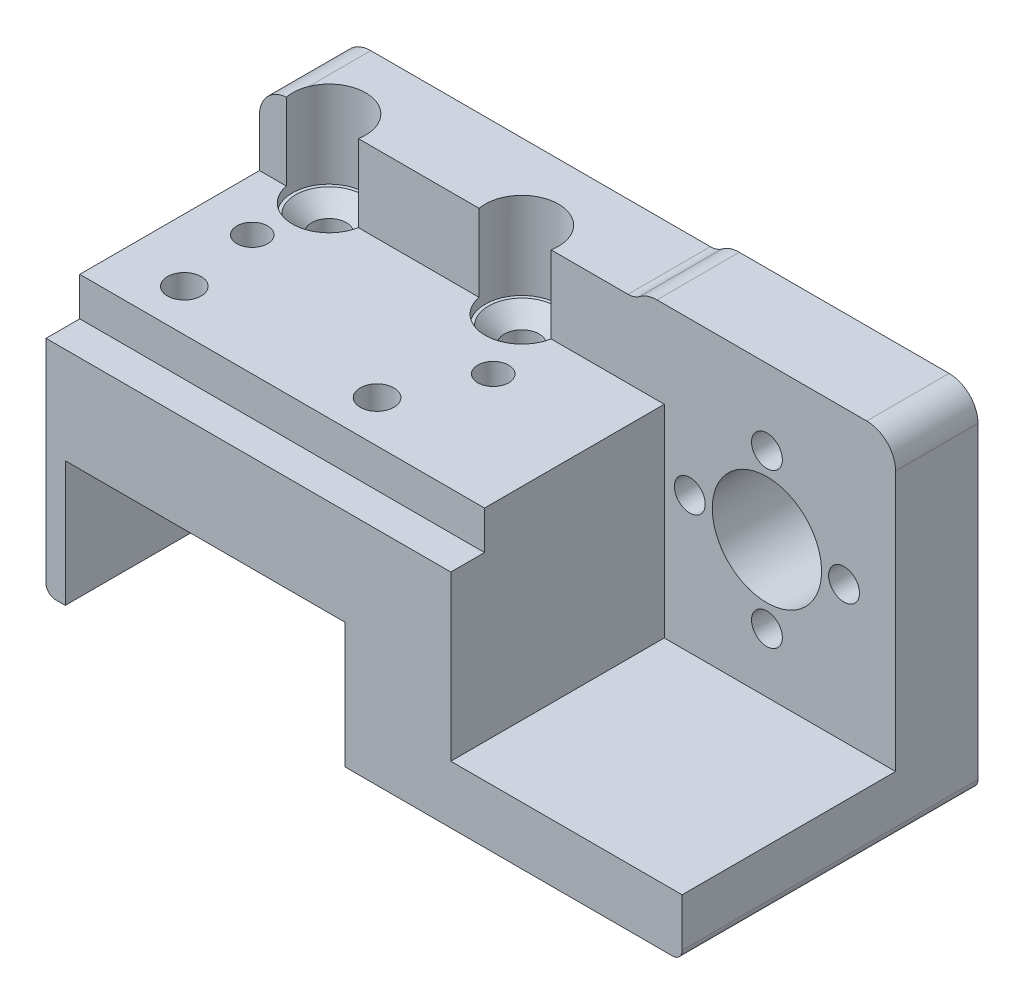
SolidWorks part; units mm, degrees
ref_plane "Front Plane" through (0, 0, 0) normal (0, 0, 1) x (1, 0, 0)
ref_plane "Top Plane" through (0, 0, 0) normal (0, 1, 0) x (1, 0, 0)
ref_plane "Right Plane" through (0, 0, 0) normal (1, 0, 0) x (0, 0, -1)
sketch "Croquis2" plane through (0, 0, 0) normal (0, 0, 1) x (1, 0, 0)
  line L0 (-42.15, -17.65) -> (-49.65, -17.65) construction
  line L1 (-42.15, -17.65) -> (-49.65, -17.65) construction
  line L2 (-49.65, -7.65) -> (-49.65, -17.65) construction
  line L3 (-49.65, -7.65) -> (-49.65, -17.65) construction
  line L5 (-52.65, -20.15) -> (13.35, -20.15)
  line L6 (-52.65, -20.15) -> (-52.65, 15.85)
  line L7 (-52.65, 15.85) -> (13.35, 15.85)
  line L8 (13.35, -20.15) -> (13.35, 15.85)
  line L9 (-50.65, -7.65) -> (-50.65, -7.15)
  line L10 (-21.65, -7.65) -> (-21.65, -17.65)
  line L11 (-21.65, -7.65) -> (-21.65, -20.15)
  line L13 (-50.65, -7.15) -> (-49.65, -7.15)
  line L14 (-21.65, -7.65) -> (-21.65, -7.15)
  line L15 (-21.65, -7.15) -> (-22.65, -7.15)
  line L16 (-50.65, -20.15) -> (-21.65, -20.15)
  line L17 (-30.45, -21.15) -> (-41.85, -21.15) construction
  line L18 (-49.65, -7.15) -> (-22.65, -7.15)
  line L19 (-49.65, -7.15) -> (-22.65, -7.15)
  line L28 (-50.65, -7.65) -> (-50.65, -17.65)
  line L29 (-50.65, -7.65) -> (-50.65, -20.15)
  circle A2 centre (0, 0) radius 5.67
  circle A3 centre (0, 0) radius 5.67
  circle A5 centre (0, 8) radius 1.3
  circle A6 centre (0, 8) radius 1.3
  circle A8 centre (8, 0) radius 1.3
  circle A9 centre (8, 0) radius 1.3
  circle A11 centre (0, -8) radius 1.3
  circle A12 centre (0, -8) radius 1.3
  circle A14 centre (-8, 0) radius 1.3
  circle A15 centre (-8, 0) radius 1.3
  circle M7 centre (0, 8) radius 1.6
  circle M8 centre (0, -8) radius 1.6
  circle M9 centre (8, 0) radius 1.6
  circle M10 centre (-8, 0) radius 1.6
  circle M12 centre (0, 0) radius 10.875
  dimension "D6" = 3
  dimension "D7" = 66
  dimension "D8" = 36
  dimension "D12" = 1
  dimension "D1" = 0.5
  dimension "D2" = 0.3
  dimension "D3" = 0.3
  dimension "D4" = 0.3
  dimension "D5" = 0.3
  dimension "D9" = 0.5
  dimension "D10" = 1
  dimension "D11" = 1
extrude "Saliente-Extruir1" add sketch "Croquis2" along normal offset from surface (30.7 mm away) 2 contours L29 L9 L13 L19 L15 L14 L11 L5 L8 L7 L6 M12 | A3 M12 M8 M10 M9 M7 region at (-20.3138, 0.0231, 0) region at (-10.5674, 0, 0)
sketch "Croquis4" plane through (0, 0, 30.7) normal (0, 0, 1) x (1, 0, 0)
  line L0 (-52.65, 15.85) -> (13.35, 15.85) construction
  line L1 (-10.65, 15.85) -> (13.35, 15.85)
  line L2 (-10.65, 15.85) -> (-10.65, -14.15)
  line L3 (-10.65, -14.15) -> (13.35, -14.15)
  line L4 (13.35, 15.85) -> (13.35, -14.15)
  line L5 (13.35, -20.15) -> (13.35, 15.85) construction
  line M9 (13.35, -20.15) -> (13.35, 15.85)
  line M10 (13.35, 15.85) -> (-52.65, 15.85)
  circle M13 centre (0, 0) radius 5.67
  circle M14 centre (0, -8) radius 1.6
  circle M15 centre (-8, 0) radius 1.6
  circle M16 centre (8, 0) radius 1.6
  circle M17 centre (0, 8) radius 1.6
  dimension "D1" = 24
  dimension "D2" = 30
extrude "Cortar-Extruir2" cut sketch "Croquis4" against normal offset from surface (22.7 mm away) 8 contours L2 L3 M9 M10 M13 M15 M17 M16 M14 region at (1.35, 15.4658, 30.7) up to face at (-27.9, -7.9, 0)
sketch "Croquis6" plane through (0, 0, 30.7) normal (0, 0, 1) x (1, 0, 0)
  line L0 (-30.15, -17.65) -> (-30.15, -13.15) construction
  line L1 (-21.65, -20.15) -> (-50.65, -20.15)
  line L2 (-21.65, -20.15) -> (-21.65, -7.15)
  line L3 (-21.65, -7.15) -> (-50.65, -7.15)
  line L4 (-50.65, -20.15) -> (-50.65, -7.15)
  line L5 (-30.15, -13.15) -> (-42.15, -13.15) construction
  line L6 (-42.15, -13.15) -> (-42.15, -17.65) construction
  line L7 (-29.65, -20.15) -> (-29.65, -12.65)
  line L8 (-29.65, -12.65) -> (-42.65, -12.65)
  line L9 (-42.65, -12.65) -> (-42.65, -20.15)
  line L10 (-29.65, -17.65) -> (-29.65, -12.65) construction
  line L11 (-42.65, -12.65) -> (-42.65, -17.65) construction
  dimension "D1" = 0.5
sketch "Croquis3" plane through (-52.65, 0, 0) normal (-1, 0, 0) x (0, 0, 1)
  line L0 (-2, -7.65) -> (32.7, -7.65) construction
  line L1 (20.85, 6.85) -> (8.55, 6.85)
  line L2 (20.85, 6.85) -> (20.85, 14.85)
  line L3 (20.85, 14.85) -> (8.55, 14.85)
  line L4 (8.55, 6.85) -> (8.55, 14.85)
  line L5 (0, -20.15) -> (0, 15.85) construction
  line L6 (30.7, 15.85) -> (30.7, -20.15) construction
  dimension "D1" = 8
  dimension "D2" = 12.3
  dimension "D3" = 14.5
  dimension "D4" = 9.85
  dimension "D5" = 8.55
extrude "Cortar-Extruir5" cut sketch "Croquis3" against normal blind 42
sketch "Croquis5" plane through (0, 15.85, 0) normal (0, 1, 0) x (1, 0, 0)
  line L2 (-52.65, -14.7) -> (-11.635, -14.7) construction
  line L3 (-10.65, -8.55) -> (-10.65, -20.85) construction
  line L4 (-52.65, -8.55) -> (-52.65, -20.85) construction
  line L5 (-52.65, -8.55) -> (-52.65, -20.85)
  circle A0 centre (-47.25, -14.7) radius 1.6
  circle A1 centre (-22.25, -14.7) radius 1.6
  point P10 (-52.65, -14.7)
  dimension "D3" = 3.2
  dimension "D1" = 11.6
  dimension "D2" = 25
extrude "Cortar-Extruir6" cut sketch "Croquis5" against normal through all contours L2 A0 | A0 L2 | A1 L2 | L2 A1 region at (-47.25, 15.85, 14.0209) region at (-22.25, 15.85, 14.0209) region at (-22.25, 15.85, 15.3791) region at (-47.25, 15.85, 15.3791)
sketch "Croquis7" plane through (0, 15.85, 0) normal (0, 1, 0) x (1, 0, 0)
  line L0 (-52.65, 0) -> (13.35, 0) construction
  line L1 (-52.65, -30.7) -> (-10.65, -30.7)
  line L2 (-52.65, -30.7) -> (-52.65, 0)
  line L3 (-52.65, 0) -> (-10.65, 0)
  line L4 (-10.65, -30.7) -> (-10.65, 0)
  line L5 (-52.65, -8.55) -> (-52.65, -20.85) construction
  line L6 (-52.65, -8.55) -> (-52.65, -20.85)
  line L8 (-52.65, -20.85) -> (-10.65, -20.85)
  line L9 (-52.65, -20.85) -> (-52.65, -30.7)
  line L10 (-52.65, -30.7) -> (-10.65, -30.7)
  line L11 (-10.65, -20.85) -> (-10.65, -30.7)
  line M3 (-10.65, -30.7) -> (-10.65, -8)
  line M6 (13.35, 0) -> (-52.65, 0)
  line M7 (-52.65, 0) -> (-52.65, -30.7)
  line M8 (-52.65, -30.7) -> (-10.65, -30.7)
  circle M15 centre (-47.25, -14.7) radius 1.6
  circle M16 centre (-22.25, -14.7) radius 1.6
extrude "Cortar-Extruir7" cut sketch "Croquis7" against normal up to surface (1 mm away) contours L2 L8 L4 M6 M7 M16 M15 region at (-31.592, 15.85, 10.345) up to face at (-47.25, 14.85, 16.3)
sketch "Croquis9" plane through (-10.65, 0, 0) normal (-1, 0, 0) x (0, 0, 1)
  line L4 (8, 14.85) -> (8, 15.85)
  line L5 (8, 15.85) -> (0, 15.85)
  line L6 (0, 15.85) -> (0, 14.85)
  line L7 (0, 14.85) -> (8, 14.85)
  line L8 (8, 14.85) -> (8, 15.85)
  line L9 (8, 15.85) -> (0, 15.85)
  line L10 (0, 15.85) -> (0, 14.85)
  line L11 (0, 14.85) -> (8, 14.85)
  dimension "D1" = 0
extrude "Saliente-Extruir4" add sketch "Croquis9" along normal blind 3
extrude "Cortar-Extruir8" cut sketch "Croquis7<3>" against normal up to surface (9 mm away) contours L8 M7 M8 M3 region at (-31.65, 15.85, 25.775) up to face at (-47.25, 6.85, 13.1)
sketch "Croquis7<3>" plane through (0, 15.85, 0) normal (0, 1, 0) x (1, 0, 0) same geometry as "Croquis7"
sketch "Croquis11" plane through (0, 6.85, 0) normal (0, 1, 0) x (1, 0, 0)
  line L1 (-47.25, -10.3121) -> (-51.05, -12.5061)
  line L2 (-51.05, -12.5061) -> (-51.05, -16.8939)
  line L3 (-51.05, -16.8939) -> (-47.25, -19.0879)
  line L4 (-47.25, -19.0879) -> (-43.45, -16.8939)
  line L5 (-43.45, -16.8939) -> (-43.45, -12.5061)
  line L6 (-43.45, -12.5061) -> (-47.25, -10.3121)
  line L7 (-22.25, -10.3121) -> (-26.05, -12.5061)
  line L8 (-26.05, -12.5061) -> (-26.05, -16.8939)
  line L9 (-26.05, -16.8939) -> (-22.25, -19.0879)
  line L10 (-22.25, -19.0879) -> (-18.45, -16.8939)
  line L11 (-18.45, -16.8939) -> (-18.45, -12.5061)
  line L12 (-18.45, -12.5061) -> (-22.25, -10.3121)
  circle A0 centre (-46.1299, -7.85) radius 1.5 construction
  circle A1 centre (-26.1299, -7.85) radius 1.5 construction
  circle A2 centre (-26.15, -22.85) radius 1.5 construction
  circle A3 centre (-46.15, -22.85) radius 1.5 construction
  circle A4 centre (-46.1299, -7.85) radius 1.5 construction
  circle A5 centre (-26.1299, -7.85) radius 1.5 construction
  circle A6 centre (-26.15, -22.85) radius 1.5 construction
  circle A7 centre (-46.15, -22.85) radius 1.5 construction
  circle A8 centre (-46.1299, -7.85) radius 3.8
  circle A9 centre (-26.1299, -7.85) radius 3.8
  circle A10 centre (-26.15, -22.85) radius 3.8
  circle A11 centre (-46.15, -22.85) radius 3.8
  circle A12 centre (-47.25, -14.7) radius 3.8 construction
  circle A13 centre (-22.25, -14.7) radius 3.8 construction
  circle A14 centre (-46.1299, -7.85) radius 1.75
  circle A15 centre (-26.1299, -7.85) radius 1.75
  circle A16 centre (-26.15, -22.85) radius 1.75
  circle A17 centre (-46.15, -22.85) radius 1.75
  circle M13 centre (-47.25, -14.7) radius 1.6
  circle M14 centre (-22.25, -14.7) radius 1.6
  line M18 (-10.65, -8.55) -> (-52.65, -8.55)
  dimension "D1" = 7.6
  dimension "D2" = 7.6
  dimension "D3" = 3.5
extrude "Cortar-Extruir9" cut sketch "Croquis11" against normal offset from surface (9 mm away) 1 from surface contours A14 A8 M18 | A14 A8 L1 L6 M18 | L1 A8 L6 | A14 M18 | A14 M18 | A15 A9 M18 | A15 M18 | A15 M18 | A15 A9 M18 region at (-46.8614, 6.85, 11.0938) region at (-46.0098, 6.85, 9.8058) region at (-26.4732, 6.85, 4.1542) region at (-26.1299, 6.85, 9.9873) region at (-46.4732, 6.85, 4.1542) region at (-46.1299, 6.85, 8.9831) region at (-46.1299, 6.85, 7.4676) region at (-26.1299, 6.85, 8.9831) region at (-26.1299, 6.85, 7.4676) up to face at (-47.25, 6.85, 13.1) offset beyond the face yes starting at face at (-25.65, 14.85, 5.5167)
extrude "Cortar-Extruir10" cut sketch "Croquis11<3>" against normal through all contours A14 M18 | A14 M18 | A15 M18 | A15 M18 | A16 | A17 region at (-46.1299, 6.85, 8.9831) region at (-46.1299, 6.85, 7.4676) region at (-26.1299, 6.85, 8.9831) region at (-26.1299, 6.85, 7.4676) region at (-26.15, 6.85, 22.85) region at (-46.15, 6.85, 22.85)
sketch "Croquis11<3>" plane through (0, 6.85, 0) normal (0, 1, 0) x (1, 0, 0) same geometry as "Croquis11"
extrude "Cortar-Extruir11" cut sketch "Croquis11<4>" along normal blind 4 and the other way through all from surface contours A8 L1 L2 L3 L4 L5 L6 M13 | L11 L12 L7 L8 L9 L10 M14 | L1 A8 L6 region at (-46.8614, 6.85, 11.0938) region at (-46.8317, 6.85, 11.6979) region at (-20.408, 6.85, 11.5096) starting at face at (-46.15, -7.15, 24.6)
sketch "Croquis11<4>" plane through (0, 6.85, 0) normal (0, 1, 0) x (1, 0, 0) same geometry as "Croquis11"
hole_wizard "Avellanado para tornillo con cabeza avellanada de clavija hexagonal de M31" positions "Croquis16" profile "Croquis17" countersink size "M3" standard "DIN" end condition through all
sketch "Croquis16" plane through (0, 5.85, 0) normal (0, 1, 0) x (1, 0, 0)
  point P0 (-46.1299, -7.85)
  point P3 (-26.1299, -7.85)
sketch "Croquis17" plane through (-46.1299, 5.85, 7.85) normal (1, 0, 0) x (0, 0, 1)
  line L0 (0, 0) -> (0, 26)
  line L1 (0, 26) -> (1.8, 26)
  line L2 (1.8, 26) -> (1.8, 1.67)
  line L3 (1.8, 1.67) -> (3.47, 0)
  line L5 (3.47, 0) -> (0, 0)
  line L6 (-1.8, 1.67) -> (-3.47, 0) construction
  line L11 (0, -6.35) -> (0, 107.95) construction
  dimension "Diámetro de taladro hasta el siguiente" = 3.6
  dimension "Profundidad de taladro hasta el siguiente" = 26
  dimension "Diámetro de avellanado cercano" = 6.94
  dimension "Ángulo de avellanado cercano" = 90
sketch "Croquis18" plane through (0, 6.85, 0) normal (0, 1, 0) x (1, 0, 0)
  line L0 (-10.65, -8.55) -> (-10.65, -30.7) construction
  line L1 (-52.65, -30.7) -> (-10.65, -30.7)
  line L2 (-52.65, -30.7) -> (-52.65, -27.2)
  line L3 (-52.65, -27.2) -> (-10.65, -27.2)
  line L4 (-10.65, -30.7) -> (-10.65, -27.2)
  dimension "D1" = 3.5
extrude "Cortar-Extruir12" cut sketch "Croquis18" against normal blind 4
sketch "Croquis19" plane through (0, 0, 8) normal (0, 0, 1) x (1, 0, 0)
  line L4 (13.35, 15.85) -> (-13.65, 15.85)
  line L6 (-10.65, 14.85) -> (-10.65, -14.15)
  line L7 (-10.65, -14.15) -> (13.35, -14.15)
  line L8 (13.35, -14.15) -> (13.35, 15.85)
  line L12 (-10.65, 14.85) -> (-10.65, -14.15)
  line L13 (-10.65, -14.15) -> (13.35, -14.15)
  line L14 (13.35, -14.15) -> (13.35, 15.85)
  line L22 (13.35, 15.85) -> (-13.65, 15.85)
  line L23 (-13.65, 15.85) -> (-13.65, 14.85)
  line L24 (-13.65, 15.85) -> (-13.65, 14.85)
  line L25 (-13.65, 14.85) -> (-10.65, 14.85)
  line L26 (-13.65, 14.85) -> (-10.65, 14.85)
  circle A0 centre (0, 0) radius 5.67 construction
  circle A1 centre (0, -8) radius 1.6 construction
  circle A2 centre (8, 0) radius 1.6 construction
  circle A3 centre (0, 8) radius 1.6 construction
  circle A4 centre (-8, 0) radius 1.6 construction
  circle A5 centre (0, 0) radius 5.67
  circle A6 centre (0, -8) radius 1.6
  circle A7 centre (8, 0) radius 1.6
  circle A8 centre (0, 8) radius 1.6
  circle A9 centre (-8, 0) radius 1.6
  dimension "D1" = 0
extrude "Saliente-Extruir5" add sketch "Croquis19" along normal up to surface (0.55 mm away) up to face at (-16.5224, 10.85, 8.55)
fillet "Redondeo1" radius 3 2 edges at (13.35, 15.85, 4.275) (-13.65, 15.85, 4.275)
fillet "Redondeo2" radius 2 1 edges at (-13.65, 14.85, 4.275)
fillet "Redondeo3" radius 3 1 edges at (-52.65, 14.85, 4.275)
fillet "Redondeo4" radius 1 2 edges at (-52.65, -20.15, 15.35) (13.35, -20.15, 15.35)
